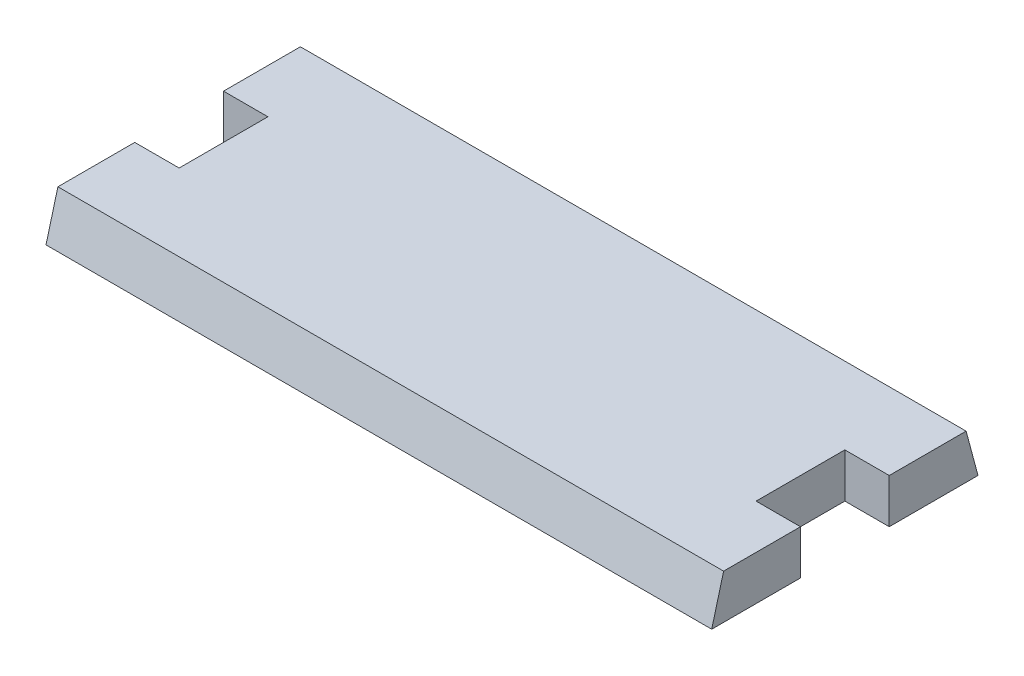
SolidWorks part; units mm, degrees
ref_plane "Front Plane" through (0, 0, 0) normal (0, 0, 1) x (1, 0, 0)
ref_plane "Top Plane" through (0, 0, 0) normal (0, 1, 0) x (1, 0, 0)
ref_plane "Right Plane" through (0, 0, 0) normal (1, 0, 0) x (0, 0, -1)
sketch "Sketch1" plane through (0, 0, 0) normal (0, 1, 0) x (1, 0, 0)
  line L1 (-75, 30) -> (75, 30)
  line L2 (-75, 30) -> (-75, -30)
  line L3 (-75, -30) -> (75, -30)
  line L4 (75, 30) -> (75, -30)
  line L5 (-75, 30) -> (75, -30) construction
  line L6 (-75, -30) -> (75, 30) construction
  point P0 (0, 0)
  dimension "D1" = 150
  dimension "D2" = 60
extrude "Boss-Extrude1" add sketch "Sketch1" along normal blind 10
chamfer "Chamfer1" distance 10 angle 15 2 edges at (0, 10, 30) (0, 10, -30) first distance on face at (0, 5, 30) first distance on face at (0, 5, -30)
sketch "Sketch2" plane through (0, 0, 0) normal (0, 1, 0) x (1, 0, 0)
  line L0 (0, 0) -> (75, 0) construction
  line L1 (75, -27.3205) -> (75, 27.3205) construction
  line L2 (0, 27.3205) -> (0, -27.3205) construction
  line L3 (75, 27.3205) -> (-75, 27.3205) construction
  line L4 (-75, -27.3205) -> (75, -27.3205) construction
  line L5 (-65, -10) -> (-85, 10) construction
  line L6 (65, 10) -> (85, 10)
  line L7 (65, 10) -> (65, -10)
  line L8 (65, -10) -> (85, -10)
  line L9 (85, 10) -> (85, -10)
  line L10 (65, 10) -> (85, -10) construction
  line L11 (65, -10) -> (85, 10) construction
  line L12 (-65, 10) -> (-85, -10) construction
  line L13 (-85, 10) -> (-85, -10)
  line L14 (-65, -10) -> (-85, -10)
  line L15 (-65, 10) -> (-65, -10)
  line L16 (-65, 10) -> (-85, 10)
  dimension "D1" = 20
  dimension "D2" = 20
extrude "Cut-Extrude3" cut sketch "Sketch2" against normal through all and the other way through all
